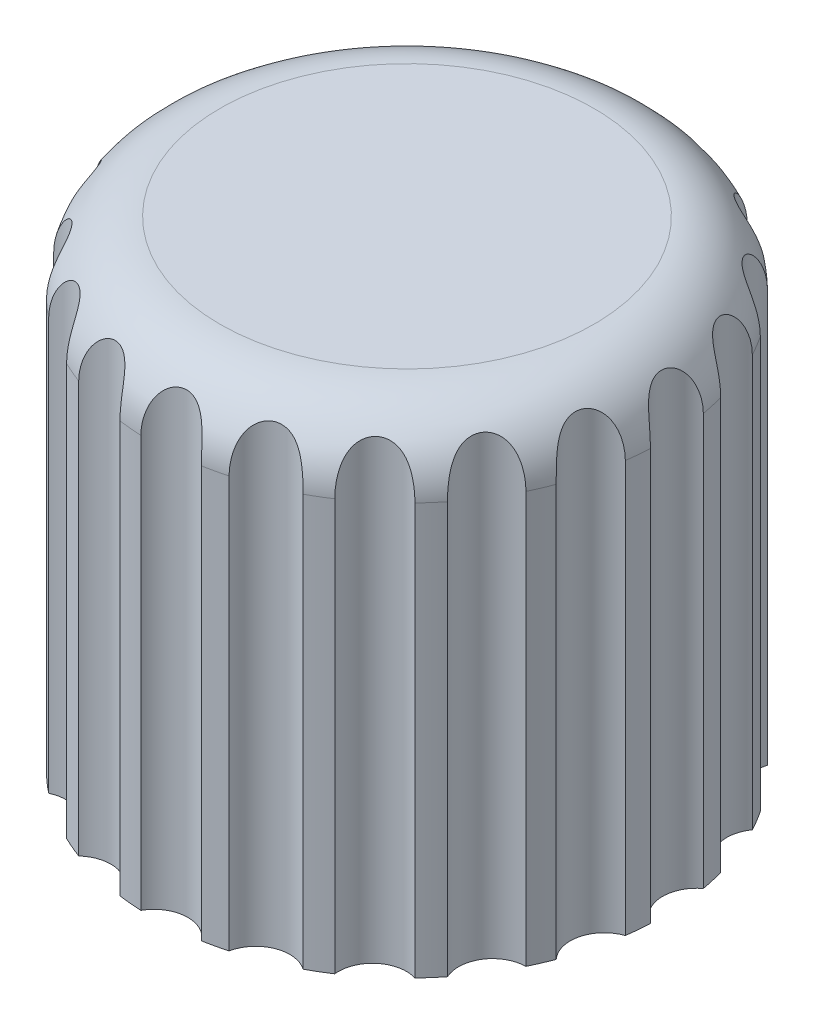
SolidWorks part; units mm, degrees
ref_plane "Front Plane" through (0, 0, 0) normal (0, 0, 1) x (1, 0, 0)
ref_plane "Top Plane" through (0, 0, 0) normal (0, 1, 0) x (1, 0, 0)
ref_plane "Right Plane" through (0, 0, 0) normal (1, 0, 0) x (0, 0, -1)
sketch "Sketch1" plane through (0, 0, 0) normal (0, 1, 0) x (1, 0, 0)
  line L0 (0, 7.5) -> (0, 0) construction
  line L1 (0, 0) -> (0, 3.75) construction
  line L2 (0, 3.75) -> (-0.4, 3.75) construction
  line L3 (0, 3.75) -> (0.4, 3.75) construction
  line L5 (-0.5, 7.4833) -> (0.5, 7.4833)
  line L6 (-0.5, 7.4833) -> (-0.5, -7.4833)
  line L7 (-0.5, -7.4833) -> (0.5, -7.4833)
  line L8 (0.5, 7.4833) -> (0.5, -7.4833)
  circle A0 centre (0, 0) radius 7.5
  circle A1 centre (0, 0) radius 5.25
  dimension "D1" = 15
  dimension "D4" = 10.5
  dimension "D2" = 0.4
  dimension "D3" = 0.4
extrude "Boss-Extrude1" add sketch "Sketch1" along normal blind 12.1 contours L6 L7 L8 L5 | A1 | A0
sketch "Sketch4" plane through (0, 12.1, 0) normal (0, 1, 0) x (1, 0, 0)
  circle A1 centre (0, 0) radius 7.5
extrude "Boss-Extrude2" add sketch "Sketch4" along normal blind 2
fillet "Fillet1" radius 2 1 edges at (0, 14.1, 7.5)
sketch "Sketch5" plane through (0, 14.1, 0) normal (0, 1, 0) x (1, 0, 0)
  circle A0 centre (0, 0) radius 8
  circle A1 centre (-6.7735, 4.2567) radius 1
  circle A2 centre (-5.1266, 6.1415) radius 1
  circle A3 centre (-2.9779, 7.4251) radius 1
  circle A4 centre (-0.5376, 7.9819) radius 1
  circle A5 centre (1.9552, 7.7574) radius 1
  circle A6 centre (4.2567, 6.7735) radius 1
  circle A7 centre (6.1415, 5.1266) radius 1
  circle A8 centre (7.4251, 2.9779) radius 1
  circle A9 centre (7.9819, 0.5376) radius 1
  circle A10 centre (7.7574, -1.9552) radius 1
  circle A11 centre (6.7735, -4.2567) radius 1
  circle A12 centre (5.1266, -6.1415) radius 1
  circle A13 centre (2.9779, -7.4251) radius 1
  circle A14 centre (0.5376, -7.9819) radius 1
  circle A15 centre (-1.9552, -7.7574) radius 1
  circle A16 centre (-4.2567, -6.7735) radius 1
  circle A17 centre (-6.1415, -5.1266) radius 1
  circle A18 centre (-7.4251, -2.9779) radius 1
  circle A19 centre (-7.9819, -0.5376) radius 1
  circle A20 centre (-7.7574, 1.9552) radius 1
  point P45 (0, 0)
  dimension "D1" = 16
  dimension "D2" = 2
  dimension "D3" = 20
extrude "Cut-Extrude1" cut sketch "Sketch5" against normal blind 20 contours A0 A20 | A0 A1 | A0 A2 | A0 A3 | A0 A4 | A0 A5 | A0 A6 | A0 A7 | A0 A8 | A0 A9 | A0 A10 | A0 A11 | A0 A12 | A0 A13 | A0 A14 | A0 A15 | A0 A16 | A0 A17 | A0 A18 | A0 A19 region at (7.5474, 14.1, -0.5084) region at (7.0209, 14.1, -2.8158) region at (7.3351, 14.1, 1.8488) region at (5.8072, 14.1, -4.8475) region at (6.4048, 14.1, 4.025) region at (4.025, 14.1, -6.4048) region at (4.8475, 14.1, 5.8072) region at (1.8488, 14.1, -7.3351) region at (2.8158, 14.1, 7.0209) region at (-0.5084, 14.1, -7.5474) region at (0.5084, 14.1, 7.5474) region at (-2.8158, 14.1, -7.0209) region at (-1.8488, 14.1, 7.3351) region at (-4.8475, 14.1, -5.8072) region at (-4.025, 14.1, 6.4048) region at (-6.4048, 14.1, -4.025) region at (-5.8072, 14.1, 4.8475) region at (-7.3351, 14.1, -1.8488) region at (-7.0209, 14.1, 2.8158) region at (-7.5474, 14.1, 0.5084)
